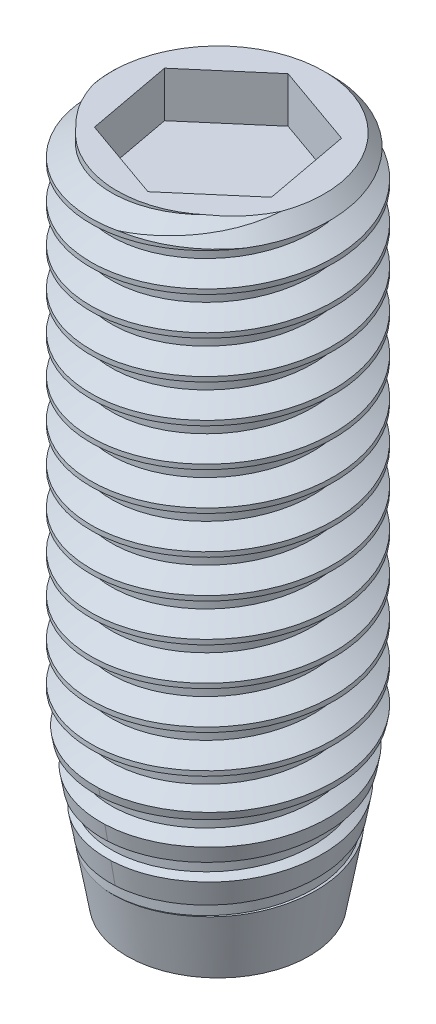
SolidWorks part; units mm, degrees
material "AISI 1020"
ref_plane "Front Plane" through (0, 0, 0) normal (0, 0, 1) x (1, 0, 0)
ref_plane "Top Plane" through (0, 0, 0) normal (0, 1, 0) x (1, 0, 0)
ref_plane "Right Plane" through (0, 0, 0) normal (1, 0, 0) x (0, 0, -1)
sketch "Sketch2" plane through (0, 0, 0) normal (0, 1, 0) x (1, 0, 0)
  circle A0 centre (0, 0) radius 4
  dimension "D1" = 8
extrude "Boss-Extrude1" add sketch "Sketch2" along normal blind 22
sketch "Sketch3" plane through (0, 22, 0) normal (0, 1, 0) x (1, 0, 0)
  line L1 (-2.7223, 0.9606) -> (-2.193, -1.8773)
  line L2 (-2.193, -1.8773) -> (0.5293, -2.8378)
  line L3 (0.5293, -2.8378) -> (2.7223, -0.9606)
  line L4 (2.7223, -0.9606) -> (2.193, 1.8773)
  line L5 (2.193, 1.8773) -> (-0.5293, 2.8378)
  line L6 (-0.5293, 2.8378) -> (-2.7223, 0.9606)
  circle A0 centre (0, 0) radius 2.5 construction
  circle A2 centre (0, 0) radius 2.5
  circle A3 centre (0, 0) radius 2.5 construction
  dimension "D1" = 1.5
extrude "Cut-Extrude1" cut sketch "Sketch3" against normal blind 1.5
chamfer "Chamfer1" distance 0.5 angle 45 1 edges at (0, 22, 4)
chamfer "Chamfer2" distance 1 angle 80 1 edges at (0, 0, 4) first distance on face at (0, 0, 4)
thread "Thread1" pitch 1.25 method cut profile "Thread Profile1" start angle 0, offset 2, length 0, pitch 1.25, diameter 8
ref_plane "Plane1" through (-4, 23.5, 0) normal (0, 0, 1) x (-1, 0, 0)
sketch "Thread Profile1" plane through (-4, 23.5, 0) normal (0, 0, 1) x (-1, 0, 0)
  line L0 (0, 0) -> (0, 1.25) construction
  line L11 (0, 0) -> (0, 1.0937)
  line L12 (0, 1.0937) -> (-0.6766, 0.7031)
  line L13 (-0.6766, 0.7031) -> (-0.6766, 0.3906)
  line L15 (-0.6766, 0.3906) -> (0, 0)
  line L17 (-0.6766, 0.5469) -> (0, 0.5469) construction
  point P2 (0, 0)
  dimension "Pitch" = 1.25
  dimension "Profile_Angle" = 60
  dimension "Profile_Land" = 0.3125
  dimension "Profile_Height" = 0.6766
